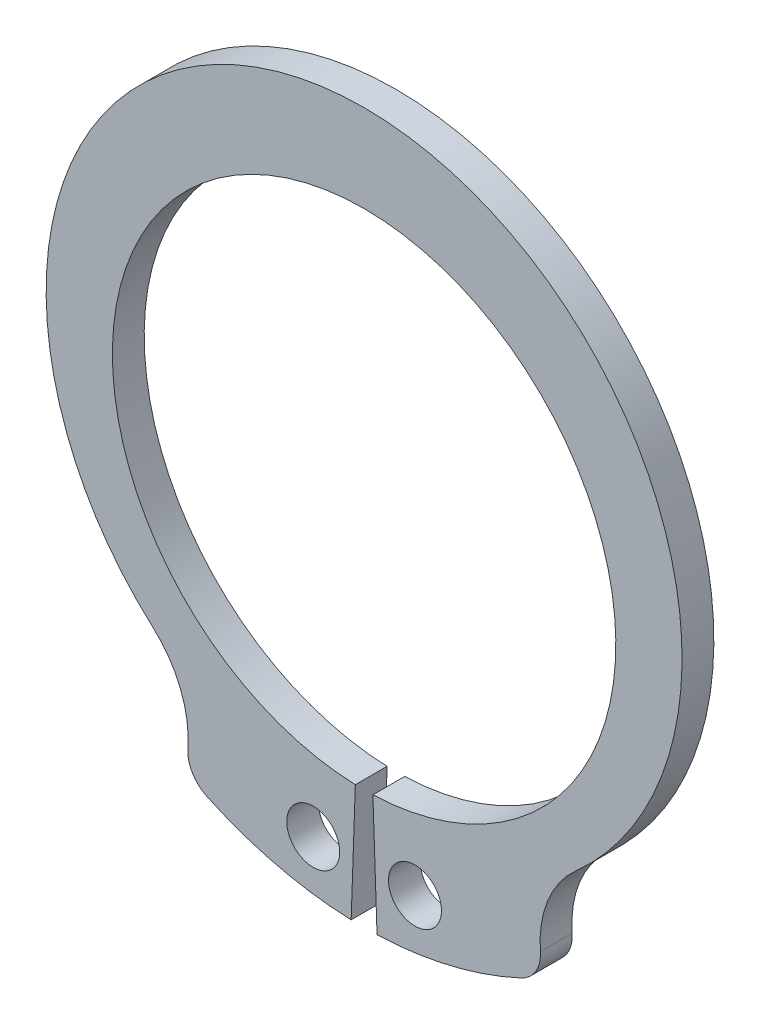
SolidWorks part; units mm, degrees
ref_plane "Front Plane" through (0, 0, 0) normal (0, 0, 1) x (1, 0, 0)
ref_plane "Top Plane" through (0, 0, 0) normal (0, 1, 0) x (1, 0, 0)
ref_plane "Right Plane" through (0, 0, 0) normal (1, 0, 0) x (0, 0, -1)
sketch "Sketch2" plane through (0, 0, 0) normal (0, 0, 1) x (1, 0, 0)
  line L0 (0, 0) -> (0, -23.75) construction
  line L1 (0, 0) -> (6.5464, -22.83)
  line L2 (0, 0) -> (-6.5464, -22.83)
  circle A0 centre (0, 0) radius 23.75
  circle A1 centre (0, -1.4) radius 20.75
  circle A6 centre (-7.7551, -17.9755) radius 2.5
  circle A7 centre (-11.896, -11.7222) radius 5
  circle A9 centre (0, -1.4) radius 15.8
  circle A10 centre (-7.7551, -17.9755) radius 1
  circle A11 centre (7.7551, -17.9755) radius 1
  circle A12 centre (7.7551, -17.9755) radius 2.5
  circle A13 centre (11.896, -11.7222) radius 5
  dimension "D1" = 47.5
  dimension "D5" = 41.5
  dimension "D2" = 10
  dimension "D6" = 5
  dimension "D7" = 31.6
  dimension "D8" = 2
  dimension "D3" = 32
  dimension "D4" = 1.4
sketch "Sketch3" plane through (0, 0, 0) normal (0, 0, 1) x (1, 0, 0)
  line L0 (0, 0) -> (0, -16.3969) construction
  line L1 (0, 0) -> (0.4886, -13.9915)
  line L2 (0, 0) -> (-0.4886, -13.9915)
  circle A0 centre (0, 0) radius 9.5
  circle A1 centre (0, 0) radius 14
  circle A2 centre (0, 0.8) radius 12
  circle A3 centre (10.6411, -11.1485) radius 4
  circle A4 centre (5.4063, -11.5471) radius 1.25
  circle A5 centre (1.9197, -11.9915) radius 1
  circle A6 centre (-10.6411, -11.1485) radius 4
  circle A7 centre (-5.4063, -11.5471) radius 1.25
  circle A8 centre (-1.9197, -11.9915) radius 1
  dimension "D1" = 19
  dimension "D2" = 24
  dimension "D3" = 0.8
  dimension "D4" = 28
  dimension "D7" = 2.5
  dimension "D8" = 8
  dimension "D11" = 2
  dimension "D5" = 2
  dimension "D6" = 5
  dimension "D9" = 1.5
  dimension "D10" = 2
extrude "Boss-Extrude1" add sketch "Sketch3" along normal blind 1.2 contours A2 A8 L2 A0 L1 A5 | A2 A8 A6 A7 A1 L2 | A7 | A5 A2 L1 A1 A4 A3 | A4 region at (7.0778, -6.835, 0) region at (3.3803, -11.9864, 0) region at (-3.3803, -11.9864, 0) region at (5.4063, -11.5471, 0) region at (-5.4063, -11.5471, 0)
equation "\"D1@Sketch2\" = \"G_anneau_alesage_rouleau\""
equation "\"c_anneau\"=31.6"
equation "\"D5@Sketch2\" = \"G_anneau_alesage_rouleau\" - 6"
equation "\"e_anneau\"=1.75"
equation "\"D2@Sketch2\"=2*\"D6@Sketch2\""
equation "\"D7@Sketch2\"=\"c_anneau\""
equation "\"d_ext_rouleau\"= 90"
equation "\"epaisseur_rouleau\"=80"
equation "\"alesage-rouleau\"= 52"
equation "\"jeu_dent_rouleau\"= 2"
equation "\"profondeur_dent_rouleau\"=4"
equation "\"n_dent_roueau\"= 15"
equation "\"d_ext_roulement_rouleau\"= 42"
equation "\"d_int_roulement_rouleau\"= 20"
equation "\"B_roulement_rouleau\"= 12"
equation "\"r_roulement_rouleau\"= 0.6"
equation "\"d_bille_roulement_rouleau\"= 8"
equation "\"F_anneau_alesage_rouleau\"=1.85"
equation "\"G_anneau_alesage_rouleau\"=47.5"
equation "\"K_anneau_alesage_rouleau\"=3.75"
equation "\"d_vis_flasque_rouleau\"=5"
equation "\"l-x_vis_flasque_rouleau\"=4"
equation "\"g_anneau_arbre_rouleau\"=19"
equation "\"f_anneau_arbre_rouleau\"=1.3"
equation "\"k_anneau_arbre_rouleau\"=1.5"
equation "\"h_matrice\"= 18"
equation "\"d_matrice\"= 220"
equation "\"d_granulat\"= 8"
equation "\"zone_vide_matrice\" = 48"
equation "\"d_alesage_matrice\"=20"
equation "\"a_clavette_alesage_matrice\"=6"
equation "\"entrax_vis_rouleau\"=65"
